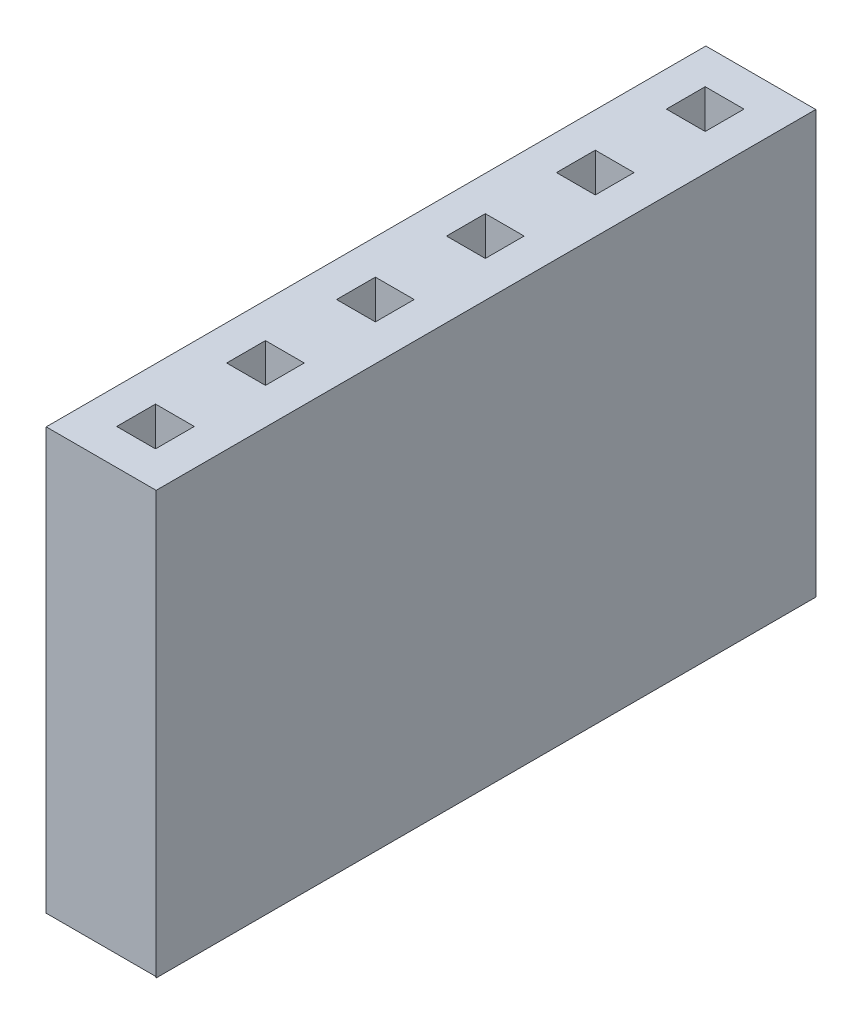
SolidWorks part; units mm, degrees
ref_plane "Front Plane" through (0, 0, 0) normal (0, 0, 1) x (1, 0, 0)
ref_plane "Top Plane" through (0, 0, 0) normal (0, 1, 0) x (1, 0, 0)
ref_plane "Right Plane" through (0, 0, 0) normal (1, 0, 0) x (0, 0, -1)
sketch "Sketch1" plane through (0, 0, 0) normal (0, 1, 0) x (1, 0, 0)
  line L1 (0, 0) -> (2.8333, 0)
  line L2 (0, 0) -> (0, 2.8333)
  line L3 (0, 2.8333) -> (2.8333, 2.8333)
  line L4 (2.8333, 0) -> (2.8333, 2.8333)
  dimension "D1" = 2.8333
other "AlignGroup1"
other "AlignGroup2"
extrude "Boss-Extrude2" add sketch "Sketch1" along normal blind 11
sketch "Sketch2" plane through (0, 0, 0) normal (0, -1, 0) x (-1, 0, 0)
  line L0 (-2.8333, 1.4167) -> (0.1648, 1.4167) construction
  line L1 (-1.9, 0.9167) -> (-0.9, 0.9167)
  line L2 (-1.9, 0.9167) -> (-1.9, 1.9167)
  line L3 (-1.9, 1.9167) -> (-0.9, 1.9167)
  line L4 (-0.9, 0.9167) -> (-0.9, 1.9167)
  line L5 (-1.9, 0.9167) -> (-0.9, 1.9167) construction
  line L6 (-1.9, 1.9167) -> (-0.9, 0.9167) construction
  line L7 (-2.8333, 0) -> (-2.8333, 2.8333) construction
  line L8 (0, 2.8333) -> (0, 0) construction
  point P0 (-1.4, 1.4167)
  dimension "D1" = 1
  dimension "D2" = 0.9
extrude "Cut-Extrude1" cut sketch "Sketch2" against normal blind 11
sketch "Sketch4" plane through (0, 0, 0) normal (0, -1, 0) x (1, 0, 0)
chamfer "Chamfer7" distance 1 angle 60 4 edges at (1.4, 0, -0.9167) (0.9, 0, -1.4167) (1.4, 0, -1.9167) (1.9, 0, -1.4167)
pattern_linear "LPattern6" count 6 spacing 2.8333 along (0, 0, 1) of "Boss-Extrude2", "Cut-Extrude1", "Chamfer7"
